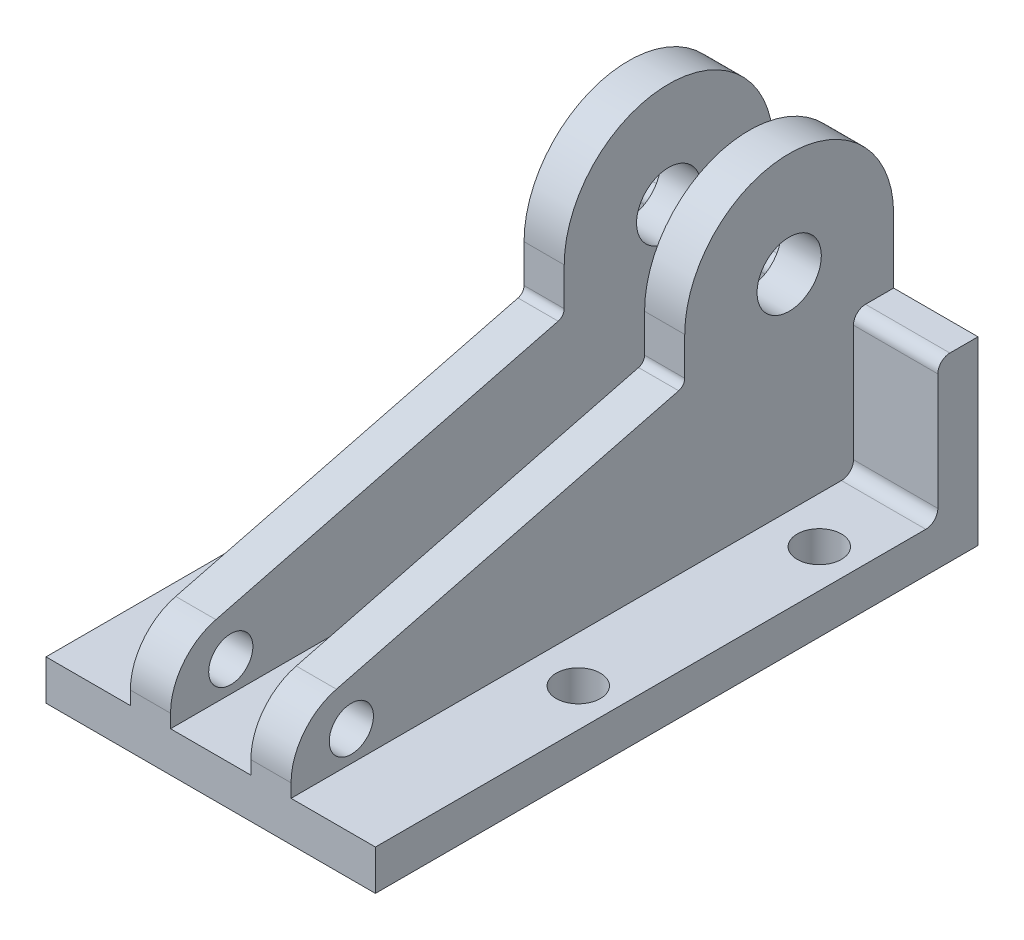
SolidWorks part; units mm, degrees
ref_plane "Front Plane" through (0, 0, 0) normal (0, 0, 1) x (1, 0, 0)
ref_plane "Top Plane" through (0, 0, 0) normal (0, 1, 0) x (1, 0, 0)
ref_plane "Right Plane" through (0, 0, 0) normal (1, 0, 0) x (0, 0, -1)
sketch "Sketch1" plane through (0, 0, 0) normal (0, 1, 0) x (1, 0, 0)
  line L1 (-41, -75) -> (41, -75)
  line L2 (-41, -75) -> (-41, 75)
  line L3 (-41, 75) -> (41, 75)
  line L4 (41, -75) -> (41, 75)
  line L5 (-41, -75) -> (41, 75) construction
  line L6 (-41, 75) -> (41, -75) construction
  point P0 (0, 0)
  dimension "D1" = 82
  dimension "D2" = 150
extrude "Boss-Extrude1" add sketch "Sketch1" along normal blind 10
sketch "Sketch2" plane through (41, 0, 0) normal (1, 0, 0) x (0, 0, -1)
  line L1 (75, 0) -> (65, 0)
  line L2 (75, 0) -> (75, 45)
  line L3 (75, 45) -> (65, 45)
  line L4 (65, 0) -> (65, 45)
  dimension "D1" = 10
  dimension "D2" = 45
extrude "Boss-Extrude2" add sketch "Sketch2" against normal through all
sketch "Sketch3" plane through (0, 0, -65) normal (0, 0, 1) x (1, 0, 0)
  line L0 (-41, 45) -> (41, 45) construction
  line L2 (10, 45) -> (10, 10)
  line L3 (10, 10) -> (20, 10)
  line L4 (20, 45) -> (20, 10)
  line L5 (-41, 10) -> (41, 10) construction
  line L6 (41, 45) -> (41, 10) construction
  line L7 (0, -55) -> (0, 55) construction
  line L9 (10, 45) -> (10, 87)
  line L10 (10, 87) -> (20, 87)
  line L11 (20, 45) -> (20, 87)
  line L12 (-10, 45) -> (-10, 87)
  line L13 (-10, 87) -> (-20, 87)
  line L14 (-20, 45) -> (-20, 87)
  line L15 (-20, 45) -> (-20, 10)
  line L16 (-10, 10) -> (-20, 10)
  line L17 (-10, 45) -> (-10, 10)
  dimension "D1" = 21
  dimension "D2" = 10
  dimension "D3" = 42
extrude "Boss-Extrude3" add sketch "Sketch3" along normal blind 42 and the other way blind 10
fillet "Fillet3" 2 edges at (15, 87, -23) (15, 87, -75) type full round first side face at (15, 48.5, -23) second side face at (0, 51.5, -75) middle face at (15, 87, -49)
fillet "Fillet4" 2 edges at (-15, 87, -23) (-15, 87, -75) type full round first side face at (-15, 48.5, -23) second side face at (0, 47.1667, -75) middle face at (-15, 87, -49)
sketch "Sketch4" plane through (20, 0, 0) normal (1, 0, 0) x (0, 0, -1)
  line L0 (23, 10) -> (23, 50)
  line L1 (23, 10) -> (23, 61) construction
  line L2 (23, 50) -> (-75, 25)
  line L3 (-75, 25) -> (-75, 10)
  line L4 (-75, 10) -> (23, 10)
  dimension "D1" = 15
  dimension "D2" = 40
extrude "Boss-Extrude4" add sketch "Sketch4" against normal up to surface (10 mm away) up to face at (10, 43, -54.3333)
sketch "Sketch5" plane through (-20, 0, 0) normal (-1, 0, 0) x (0, 0, 1)
  line L0 (-23, 50) -> (75, 25)
  line L1 (75, 25) -> (75, 10)
  line L2 (75, 10) -> (-23, 10)
  line L3 (-23, 10) -> (-23, 50)
extrude "Boss-Extrude5" add sketch "Sketch5" against normal up to surface (10 mm away) up to face at (-10, 43, -54.3333)
fillet "Fillet5" radius 15 1 edges at (15, 25, 75)
fillet "Fillet6" radius 15 1 edges at (-15, 25, 75)
sketch "Sketch6" plane through (20, 0, 0) normal (1, 0, 0) x (0, 0, -1)
  line L0 (65, 10) -> (-75, 10) construction
  line L1 (-75, 10) -> (-75, 0) construction
  circle A0 centre (49, 61) radius 8
  circle A1 centre (-60, 17.5) radius 5.5
  dimension "D1" = 7.5
  dimension "D3" = 11
  dimension "D2" = 15
extrude "Cut-Extrude1" cut sketch "Sketch6" against normal through all
fillet "Fillet7" radius 3 1 edges at (30.5, 45, -65)
fillet "Fillet8" radius 3 1 edges at (0, 45, -65)
fillet "Fillet9" radius 3 1 edges at (-30.5, 45, -65)
fillet "Fillet10" radius 3 3 edges at (-30.5, 10, -65) (0, 10, -65) (30.5, 10, -65)
fillet "Fillet11" radius 2 2 edges at (-15, 50, -23) (15, 50, -23)
sketch "Sketch7" plane through (0, 10, 0) normal (0, 1, 0) x (1, 0, 0)
  line L0 (20, 75) -> (41, 75) construction
  line L1 (20, 62) -> (20, -75) construction
  line L3 (20, 21.4944) -> (20, -63.7078) construction
  line L4 (0, -55) -> (0, 55) construction
  circle A0 centre (31.5, 45) radius 5.5
  circle A1 centre (31.5, -15) radius 5.5
  circle A2 centre (-31.5, -15) radius 5.5
  circle A3 centre (-31.5, 45) radius 5.5
  dimension "D1" = 30
  dimension "D3" = 11
  dimension "D4" = 11.5
  dimension "D6" = 11
  dimension "D2" = 11.5
  dimension "D5" = 60
extrude "Cut-Extrude2" cut sketch "Sketch7" against normal through all
ref_plane "Plane1" through (10, 0, 0) normal (-1, 0, 0) x (0, 0, 1)
ref_plane "Plane2" through (-20, 0, 0) normal (-1, 0, 0) x (0, 0, 1)
